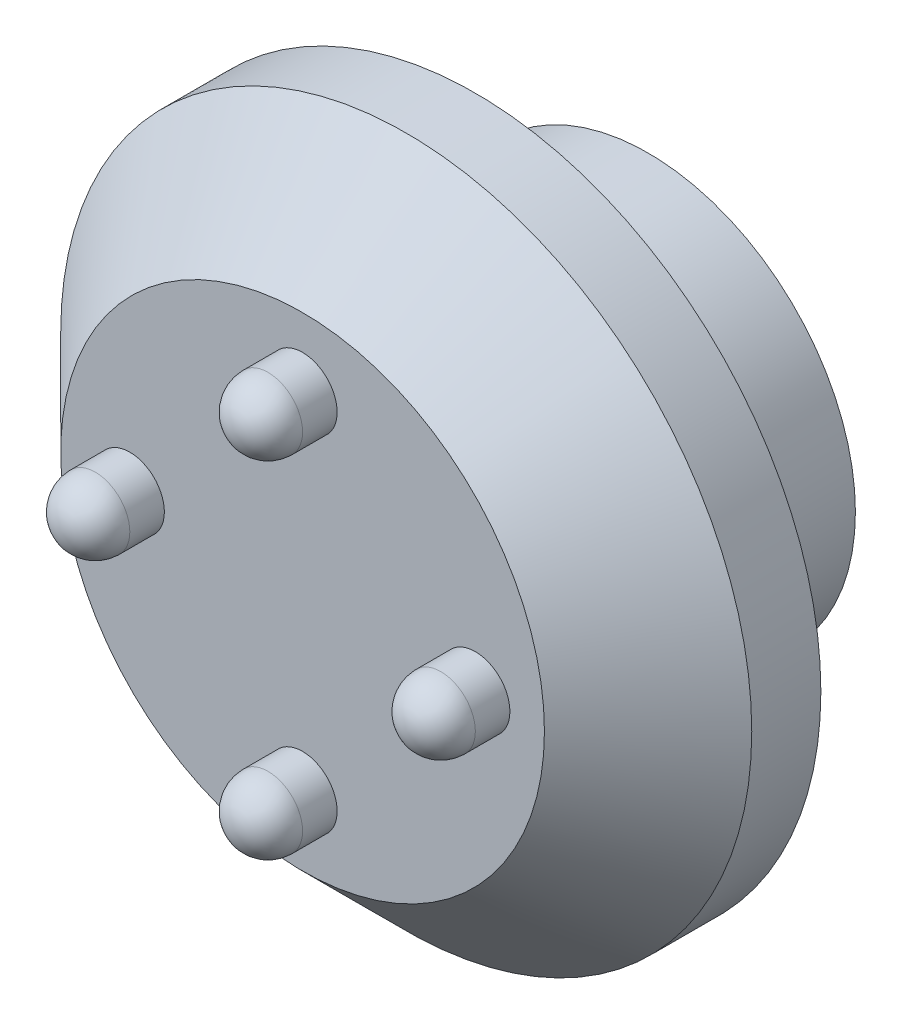
SolidWorks part; units mm, degrees
ref_plane "Front Plane" through (0, 0, 0) normal (0, 0, 1) x (1, 0, 0)
ref_plane "Top Plane" through (0, 0, 0) normal (0, 1, 0) x (1, 0, 0)
ref_plane "Right Plane" through (0, 0, 0) normal (1, 0, 0) x (0, 0, -1)
sketch "Sketch1" plane through (0, 0, 0) normal (0, 0, 1) x (1, 0, 0)
  circle A0 centre (0, 0) radius 3.25 construction
  circle A1 centre (0, 0) radius 3.25
  circle A2 centre (0, 0) radius 6 construction
  circle A3 centre (0, 0) radius 6
extrude "Boss-Extrude1" add sketch "Sketch1" against normal blind 5 and the other way blind 5
sketch "Sketch2" plane through (0, 0, 0) normal (0, 0, 1) x (1, 0, 0)
  circle A0 centre (0, 0) radius 10
extrude "Boss-Extrude2" add sketch "Sketch2" along normal blind 5
chamfer "Chamfer1" distance 3 angle 45 1 edges at (10, 0, 5)
sketch "Sketch3" plane through (0, 0, 5) normal (0, 0, 1) x (1, 0, 0)
  line L0 (0, 0) -> (0, 5) construction
  circle A0 centre (0, 0) radius 5 construction
  circle A1 centre (0, 5) radius 1
  circle A2 centre (5, 0) radius 1
  circle A3 centre (0, -5) radius 1
  circle A4 centre (-5, 0) radius 1
  point P14 (0, 0)
  dimension "D1" = 4
extrude "Boss-Extrude3" add sketch "Sketch3" along normal blind 2 separate body
fillet "Fillet1" radius 1 1 edges at (-4, 0, 7)
fillet "Fillet2" radius 1 1 edges at (1, -5, 7)
fillet "Fillet3" radius 1 1 edges at (6, 0, 7)
fillet "Fillet4" radius 1 1 edges at (1, 5, 7)
